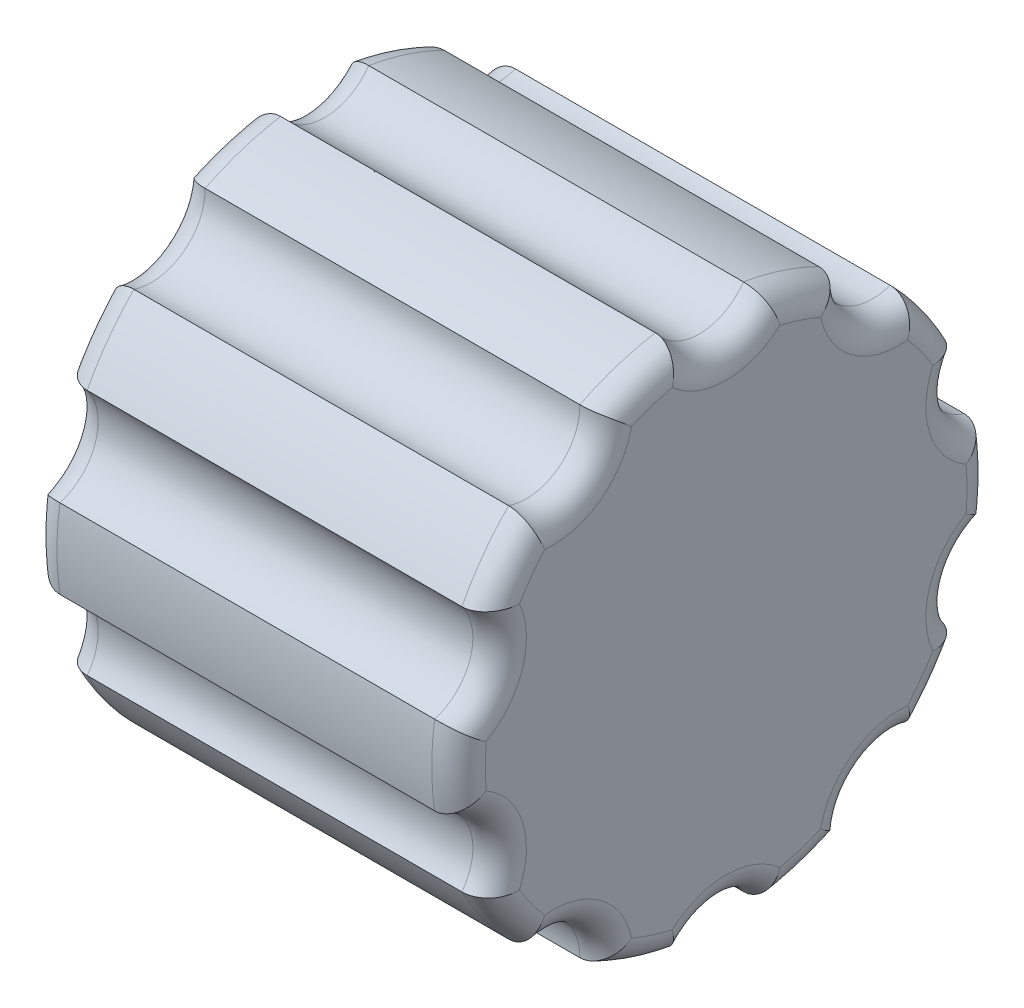
SolidWorks part; units mm, degrees
ref_plane "Front Plane" through (0, 0, 0) normal (0, 0, 1) x (1, 0, 0)
ref_plane "Top Plane" through (0, 0, 0) normal (0, 1, 0) x (1, 0, 0)
ref_plane "Right Plane" through (0, 0, 0) normal (1, 0, 0) x (0, 0, -1)
sketch "Sketch1" plane through (0, 0, 0) normal (1, 0, 0) x (0, 0, -1)
  line L2 (0, 0) -> (0, 19.2914) construction
  line L5 (0, 0) -> (19.2914, 0) construction
  line L8 (0, 0) -> (0, -19.2914) construction
  line L11 (0, 0) -> (-19.2914, 0) construction
  circle A0 centre (0, 0) radius 5
  arc A1 (-0.8229, 4.9318) -> (0.8229, 4.9318) centre (0, 5.5) ccw
  arc A2 (2.2331, 4.4736) -> (3.5646, 3.5062) centre (3.2328, 4.4496) ccw
  arc A3 (4.4361, 2.3066) -> (4.9447, 0.7414) centre (5.2308, 1.6996) ccw
  arc A4 (4.9447, -0.7414) -> (4.4361, -2.3066) centre (5.2308, -1.6996) ccw
  arc A5 (3.5646, -3.5062) -> (2.2331, -4.4736) centre (3.2328, -4.4496) ccw
  arc A6 (0.8229, -4.9318) -> (-0.8229, -4.9318) centre (0, -5.5) ccw
  arc A7 (-2.2331, -4.4736) -> (-3.5646, -3.5062) centre (-3.2328, -4.4496) ccw
  arc A8 (-4.4361, -2.3066) -> (-4.9447, -0.7414) centre (-5.2308, -1.6996) ccw
  arc A9 (-4.9447, 0.7414) -> (-4.4361, 2.3066) centre (-5.2308, 1.6996) ccw
  arc A10 (-3.5646, 3.5062) -> (-2.2331, 4.4736) centre (-3.2328, 4.4496) ccw
  point P6 (0, 4.6604)
  point P7 (-0.7642, 5.9511)
  point P35 (0, 0)
  point P36 (0, 5.247)
  point P37 (-3.0841, -4.2449)
  point P38 (0, 4.9604)
  point P57 (0, 0)
  dimension "D1" = 10
  dimension "D2" = 1
  dimension "D5" = 4
  dimension "D3" = 5.5
  dimension "D4" = 10
extrude "Boss-Extrude1" add sketch "Sketch1" along normal blind 8 contours A10 A0 A9 A8 A7 A6 A5 A4 A3 A2 A1 region at (0, 0, 0)
fillet "Fillet1" radius 0.5 40 edges at (0, 2.9389, 4.0451) (0, 1.3906, 4.2798) (0, 0, 5) (0, -1.3906, 4.2798) (0, -2.9389, 4.0451) (0, -3.6406, 2.645) (0, -4.7553, 1.5451) (0, -4.5, 0) (0, -4.7553, -1.5451) (0, -3.6406, -2.645) (0, -2.9389, -4.0451) (0, -1.3906, -4.2798) (0, 0, -5) (0, 1.3906, -4.2798) (0, 2.9389, -4.0451) (0, 3.6406, -2.645) (0, 4.7553, -1.5451) (0, 4.5, 0) (0, 4.7553, 1.5451) (0, 3.6406, 2.645) (8, 4.7553, 1.5451) (8, 4.5, 0) (8, 4.7553, -1.5451) (8, 3.6406, -2.645) (8, 2.9389, -4.0451) (8, 1.3906, -4.2798) (8, 0, -5) (8, -1.3906, -4.2798) (8, -2.9389, -4.0451) (8, -3.6406, -2.645) (8, -4.7553, -1.5451) (8, -4.5, 0) (8, -4.7553, 1.5451) (8, -3.6406, 2.645) (8, -2.9389, 4.0451) (8, -1.3906, 4.2798) (8, 0, 5) (8, 1.3906, 4.2798) (8, 2.9389, 4.0451) (8, 3.6406, 2.645)
sketch "Sketch3" plane through (0, 0, 0) normal (-1, 0, 0) x (0, 0, 1)
  line L1 (1.5011, 0) -> (0.7506, 1.3)
  line L2 (0.7506, 1.3) -> (-0.7506, 1.3)
  line L3 (-0.7506, 1.3) -> (-1.5011, 0)
  line L4 (-1.5011, 0) -> (-0.7506, -1.3)
  line L5 (-0.7506, -1.3) -> (0.7506, -1.3)
  line L6 (0.7506, -1.3) -> (1.5011, 0)
  circle A0 centre (0, 0) radius 2.75
  circle A1 centre (0, 0) radius 4.75
  circle A2 centre (0, 0) radius 1.3 construction
  dimension "D1" = 5.5
  dimension "D3" = 2.6
  dimension "D2" = 2
extrude "Cut-Extrude1" cut sketch "Sketch3" against normal blind 3.2 contours A0 L6 L5 L4 L3 L2 L1 region at (0, 0, -2.6722)
extrude "Cut-Extrude3" cut sketch "Sketch3<7>" against normal blind 1.6 contours L4 L5 L6 L1 L2 L3
sketch "Sketch3<7>" plane through (0, 0, 0) normal (-1, 0, 0) x (0, 0, 1) same geometry as "Sketch3"
